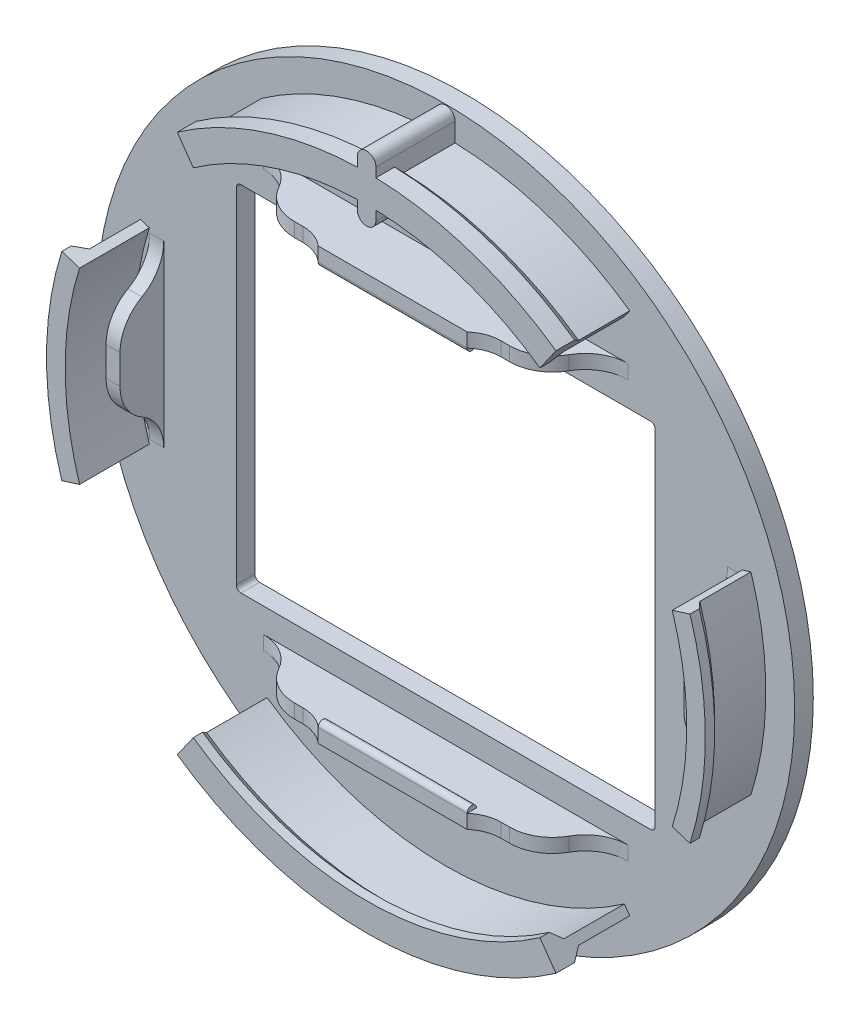
SolidWorks part; units mm, degrees
ref_plane "Plan de face" through (0, 0, 0) normal (0, 0, 1) x (1, 0, 0)
ref_plane "Plan de dessus" through (0, 0, 0) normal (0, 1, 0) x (1, 0, 0)
ref_plane "Plan de droite" through (0, 0, 0) normal (1, 0, 0) x (0, 0, -1)
sketch "Esquisse1" plane through (0, 0, 0) normal (0, 0, 1) x (1, 0, 0)
  line L1 (-22, -19) -> (22, -19)
  line L2 (-22.5, -18.5) -> (-22.5, 18.5)
  line L3 (-22, 19) -> (22, 19)
  line L4 (22.5, -18.5) -> (22.5, 18.5)
  line L5 (-22.5, -19) -> (22.5, 19) construction
  line L6 (-22.5, 19) -> (22.5, -19) construction
  circle A0 centre (0, 0) radius 37.5
  arc A1 (-22, 19) -> (-22.5, 18.5) centre (-22, 18.5) ccw
  arc A2 (22.5, 18.5) -> (22, 19) centre (22, 18.5) ccw
  arc A3 (22, -19) -> (22.5, -18.5) centre (22, -18.5) ccw
  arc A4 (-22.5, -18.5) -> (-22, -19) centre (-22, -18.5) ccw
  dimension "D1" = 75
  dimension "D4" = 0.5
  dimension "D5" = 0.5
  dimension "D6" = 0.5
  dimension "D7" = 0.5
  dimension "D2" = 45
  dimension "D3" = 38
extrude "Boss.-Extru.1" add sketch "Esquisse1" along normal blind 2
sketch "Esquisse2" plane through (0, 0, 2) normal (0, 0, 1) x (1, 0, 0)
  line L0 (-15, 22.4) -> (15, 22.4)
  line L1 (0, 0) -> (0, 13.5473) construction
  line L2 (0, 0) -> (12.5796, 0) construction
  line L3 (31.05, -5) -> (31.05, 5)
  line L4 (-31.05, -5) -> (-31.05, 5)
  line L5 (-15, -22.4) -> (15, -22.4)
  point P2 (0, 22.4)
  point P9 (31.05, 0)
  dimension "D1" = 30
  dimension "D2" = 10
  dimension "D3" = 44.8
  dimension "D4" = 62.1
extrude "Extru.-Mince1" add sketch "Esquisse2" along normal blind 4.7 thin thin type mid plane wall 1.5
sketch "Esquisse5" plane through (0, 0, 6.7) normal (0, 0, 1) x (1, 0, 0)
  line L0 (-15, 23.15) -> (15, 23.15) construction
  line L1 (-8, 23.15) -> (8, 23.15)
  line L2 (-8, 23.15) -> (-8, 21.15)
  line L3 (-8, 21.15) -> (8, 21.15)
  line L4 (8, 23.15) -> (8, 21.15)
  line L5 (0, 0) -> (15.9238, 0) construction
  line L6 (8, -23.15) -> (8, -21.15)
  line L7 (-8, -21.15) -> (8, -21.15)
  line L8 (-8, -23.15) -> (-8, -21.15)
  line L9 (-8, -23.15) -> (8, -23.15)
  line L10 (-15, 21.65) -> (15, 21.65) construction
  point P7 (0, 23.15)
  dimension "D1" = 0.5
  dimension "D2" = 16
extrude "Boss.-Extru.3" add sketch "Esquisse5" along normal blind 1
fillet "Congé5" radius 0.5 6 edges at (-8, 21.4, 6.7) (0, 21.15, 6.7) (-8, 21.15, 7.2) (8, 21.4, 6.7) (8, 21.15, 7.2) (0, 21.15, 7.7)
fillet "Congé6" radius 0.5 6 edges at (8, -21.4, 6.7) (0, -21.15, 6.7) (8, -21.15, 7.2) (-8, -21.4, 6.7) (-8, -21.15, 7.2) (0, -21.15, 7.7)
chamfer "Chanfrein2" [suppressed] distance 0.5 angle 45
chamfer "Chanfrein5" [suppressed] distance 1 angle 45
fillet "Congé1" radius 4.6 8 edges at (31.05, 5, 2) (-15, -22.4, 2) (15, -22.4, 2) (31.05, -5, 2) (-15, 22.4, 2) (15, 22.4, 2) (-31.05, 5, 2) (-31.05, -5, 2)
fillet "Congé2" radius 4.6 8 edges at (15, 22.4, 6.7) (31.05, 5, 6.7) (31.05, -5, 6.7) (15, -22.4, 6.7) (-15, -22.4, 6.7) (-31.05, 5, 6.7) (-31.05, -5, 6.7) (-15, 22.4, 6.7)
sketch "Esquisse3" plane through (0, 0, 2) normal (0, 0, 1) x (1, 0, 0)
  line L0 (-31.8, 5.5878) -> (-31.8, 1.5757) construction
  line L1 (-32.8, -28.15) -> (32.8, -28.15)
  line L2 (-32.8, -28.15) -> (-32.8, 28.15)
  line L3 (-32.8, 28.15) -> (32.8, 28.15)
  line L4 (32.8, -28.15) -> (32.8, 28.15)
  line L5 (-32.8, -28.15) -> (32.8, 28.15) construction
  line L6 (-32.8, 28.15) -> (32.8, -28.15) construction
  line L8 (-19.6, 23.15) -> (19.6, 23.15) construction
  arc A0 (-32.8, 10.3692) -> (-32.8, -10.3692) centre (0, 0) ccw
  arc A1 (-19.7721, -28.15) -> (19.7721, -28.15) centre (0, 0) ccw
  arc A2 (32.8, -10.3692) -> (32.8, 10.3692) centre (0, 0) ccw
  arc A3 (19.7721, 28.15) -> (-19.7721, 28.15) centre (0, 0) ccw
  dimension "D1" = 68.8
  dimension "D2" = 5
  dimension "D3" = 1
extrude "Extru.-Mince2" add sketch "Esquisse3" along normal blind 6.5 thin contours A3 | A1 | A2 | A0
sketch "Esquisse4" plane through (0, 0, 8.5) normal (0, 0, 1) x (1, 0, 0)
  line L16 (-19.1974, 27.3317) -> (-20.3469, 28.9683)
  line L17 (-19.1974, 27.3317) -> (-19.7721, 28.15) construction
  line L18 (20.3469, 28.9683) -> (19.1974, 27.3317)
  line L19 (19.7721, 28.15) -> (19.1974, 27.3317) construction
  line L20 (33.7535, 10.6706) -> (31.8465, 10.0678)
  line L21 (31.8465, 10.0678) -> (32.8, 10.3692) construction
  line L22 (33.7535, -10.6706) -> (31.8465, -10.0678)
  line L23 (32.8, -10.3692) -> (31.8465, -10.0678) construction
  line L24 (19.1974, -27.3317) -> (20.3469, -28.9683)
  line L25 (19.1974, -27.3317) -> (19.7721, -28.15) construction
  line L26 (-19.1974, -27.3317) -> (-20.3469, -28.9683)
  line L27 (-19.7721, -28.15) -> (-19.1974, -27.3317) construction
  line L28 (-31.8465, -10.0678) -> (-33.7535, -10.6706)
  line L29 (-31.8465, -10.0678) -> (-32.8, -10.3692) construction
  line L30 (-31.8465, 10.0678) -> (-33.7535, 10.6706)
  line L31 (-32.8, 10.3692) -> (-31.8465, 10.0678) construction
  arc A2 (-31.8465, 10.0678) -> (-31.8465, -10.0678) centre (0, 0) ccw
  arc A6 (-33.7535, 10.6706) -> (-33.7535, -10.6706) centre (0, 0) ccw
  arc A14 (19.1974, 27.3317) -> (-19.1974, 27.3317) centre (0, 0) ccw construction
  arc A15 (19.7721, 28.15) -> (-19.7721, 28.15) centre (0, 0) ccw construction
  arc A16 (19.1974, 27.3317) -> (-19.1974, 27.3317) centre (0, 0) ccw
  arc A17 (20.3469, 28.9683) -> (-20.3469, 28.9683) centre (0, 0) ccw
  arc A18 (33.7535, -10.6706) -> (33.7535, 10.6706) centre (0, 0) ccw
  arc A19 (31.8465, -10.0678) -> (31.8465, 10.0678) centre (0, 0) ccw
  arc A20 (-19.1974, -27.3317) -> (19.1974, -27.3317) centre (0, 0) ccw
  arc A21 (-20.3469, -28.9683) -> (20.3469, -28.9683) centre (0, 0) ccw
  dimension "D1" = 0
  dimension "D2" = 1
extrude "Boss.-Extru.2" add sketch "Esquisse4" along normal blind 1
sketch "Esquisse8" plane through (0, 0, 9.5) normal (0, 0, 1) x (1, 0, 0)
  line L1 (20.3469, -28.9683) -> (18.6226, -26.5134)
  line L2 (-20.3469, -28.9683) -> (-18.6226, -26.5134)
  line L5 (-20.3469, 28.9683) -> (-18.6226, 26.5134)
  line L6 (20.3469, 28.9683) -> (18.6226, 26.5134)
  line L11 (20.3469, -28.9683) -> (19.1974, -27.3317) construction
  line L12 (-19.1974, -27.3317) -> (-20.3469, -28.9683) construction
  line L15 (-19.1974, 27.3317) -> (-19.7721, 28.15) construction
  line L16 (19.1974, 27.3317) -> (20.3469, 28.9683) construction
  arc A2 (-20.3469, -28.9683) -> (20.3469, -28.9683) centre (0, 0) ccw construction
  arc A3 (-19.1974, -27.3317) -> (19.1974, -27.3317) centre (0, 0) ccw construction
  arc A4 (18.6226, 26.5134) -> (-18.6226, 26.5134) centre (0, 0) ccw
  arc A5 (20.3469, 28.9683) -> (-20.3469, 28.9683) centre (0, 0) ccw
  arc A8 (-18.6226, -26.5134) -> (18.6226, -26.5134) centre (0, 0) ccw
  arc A9 (-20.3469, -28.9683) -> (20.3469, -28.9683) centre (0, 0) ccw
  arc A10 (19.1974, 27.3317) -> (-19.1974, 27.3317) centre (0, 0) ccw construction
  arc A11 (20.3469, 28.9683) -> (-20.3469, 28.9683) centre (0, 0) ccw construction
  dimension "D1" = 1
  dimension "D2" = 1
extrude "Boss.-Extru.5" add sketch "Esquisse8" along normal blind 1
sketch "Esquisse7" plane through (0, 0, 2) normal (0, 0, 1) x (1, 0, 0)
  line L0 (0, 36.4) -> (0, 31.4) construction
  line L5 (1, 36.4) -> (1, 31.4)
  line L6 (-1, 36.4) -> (-1, 31.4)
  line L7 (0, 37.5) -> (0, 33.9) construction
  arc A0 (1, 36.4) -> (-1, 36.4) centre (0, 36.4) ccw
  arc A3 (-1, 31.4) -> (1, 31.4) centre (0, 31.4) ccw
  circle A5 centre (0, 0) radius 37.5 construction
  point P2 (0, 33.9)
  dimension "D3" = 3.6
  dimension "D1" = 2
  dimension "D2" = 5
extrude "Boss.-Extru.4" add sketch "Esquisse7" along normal up to surface (8.5 mm away)
chamfer "Chanfrein1" distance 1 angle 45 24 edges at (10.8439, 32.6461, 8.5) (0, -34.4, 8.5) (34.4, 0, 8.5) (-34.4, 0, 8.5) (20.0595, 28.5592, 8.5) (-20.0595, 28.5592, 8.5) (-10.5425, 31.6925, 9.5) (33.2767, 10.5199, 8.5) (33.2767, -10.5199, 8.5) (-20.0595, -28.5592, 8.5) (20.0595, -28.5592, 8.5) (0, -33.4, 9.5) (-33.2767, 10.5199, 8.5) (-33.2767, -10.5199, 8.5) (18.91, -26.9225, 9.5) (-18.91, -26.9225, 9.5) (-18.91, 26.9225, 9.5) (18.91, 26.9225, 9.5) (10.5425, 31.6925, 9.5) (-10.8439, 32.6461, 8.5) (-1, 34.8857, 8.5) (1, 34.8857, 8.5) (-1, 32.8848, 9.5) (1, 32.8848, 9.5)
fillet "Congé4" [suppressed] radius 5
fillet "Congé7" radius 4 4 edges at (8, -22.4, 6.7) (-8, -22.4, 6.7) (-8, 22.4, 6.7) (8, 22.4, 6.7)
equation "\"D4@Esquisse2\"=60.60mm+1.5"
equation "\"D3@Esquisse2\"=43.30mm+1.5"
